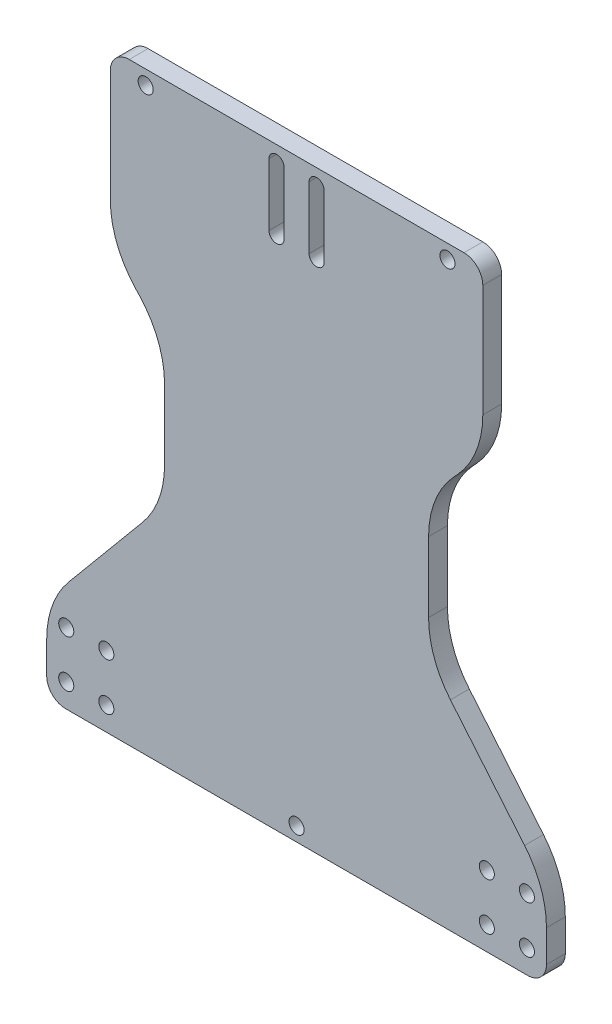
SolidWorks part; units mm, degrees
material "Acrylic (Medium-high impact)"
ref_plane "Front Plane" through (0, 0, 0) normal (0, 0, 1) x (1, 0, 0)
ref_plane "Top Plane" through (0, 0, 0) normal (0, 1, 0) x (1, 0, 0)
ref_plane "Right Plane" through (0, 0, 0) normal (1, 0, 0) x (0, 0, -1)
sketch "Sketch1" plane through (0, 0, 0) normal (0, 0, 1) x (1, 0, 0)
  line L0 (-0.75, 63) -> (106.75, 63) construction
  line L1 (0, 0) -> (106, 0)
  line L2 (0, 0) -> (0, 18)
  line L3 (81, 48) -> (81, 78)
  line L4 (106, 18) -> (81, 48)
  line L5 (0, 18) -> (25, 48)
  line L6 (25, 48) -> (25, 78)
  line L7 (106, 0) -> (106, 18)
  line L8 (53, 0) -> (53, 63) construction
  line L9 (13.5, 126) -> (13.5, 90.3404)
  line L10 (13.5, 90.3404) -> (25, 78)
  line L11 (92.5, 90.3404) -> (81, 78)
  line L12 (92.5, 126) -> (92.5, 90.3404)
  line L13 (13.5, 126) -> (92.5, 126)
  line L14 (12.65, 10) -> (4.15, 10) construction
  line L15 (4.15, 5) -> (12.65, 5) construction
  line L16 (4.15, 5) -> (4.15, 15) construction
  line L17 (4.15, 15) -> (12.65, 15) construction
  line L18 (12.65, 5) -> (12.65, 15) construction
  line L19 (53, 126) -> (53, 122.6) construction
  line L20 (48.75, 122.6) -> (57.25, 122.6) construction
  line L21 (48.75, 122.6) -> (48.75, 109.4) construction
  line L22 (48.75, 109.4) -> (57.25, 109.4) construction
  line L23 (57.25, 122.6) -> (57.25, 109.4) construction
  line L24 (48.75, 116) -> (57.25, 116) construction
  line L25 (48.75, 122.6) -> (48.75, 109.4) construction
  line L26 (50.35, 122.6) -> (50.35, 109.4)
  line L27 (47.15, 122.6) -> (47.15, 109.4)
  line L28 (57.25, 109.4) -> (57.25, 122.6) construction
  line L29 (55.65, 109.4) -> (55.65, 122.6)
  line L30 (58.85, 109.4) -> (58.85, 122.6)
  circle A0 centre (4.15, 5) radius 1.6
  circle A1 centre (12.65, 5) radius 1.6
  circle A2 centre (12.65, 15) radius 1.6
  circle A3 centre (4.15, 15) radius 1.6
  circle A4 centre (101.85, 5) radius 1.6
  circle A5 centre (93.35, 5) radius 1.6
  circle A6 centre (93.35, 15) radius 1.6
  circle A7 centre (101.85, 15) radius 1.6
  circle A8 centre (53, 3) radius 1.6
  circle A9 centre (21, 123) radius 1.6
  circle A10 centre (85, 123) radius 1.6
  arc A12 (50.35, 122.6) -> (47.15, 122.6) centre (48.75, 122.6) ccw
  arc A13 (47.15, 109.4) -> (50.35, 109.4) centre (48.75, 109.4) ccw
  arc A14 (55.65, 109.4) -> (58.85, 109.4) centre (57.25, 109.4) ccw
  arc A15 (58.85, 122.6) -> (55.65, 122.6) centre (57.25, 122.6) ccw
  point P16 (25, 63)
  point P18 (81, 63)
  point P51 (48.75, 116)
  point P56 (57.25, 116)
  dimension "D10" = 3.2
  dimension "D15" = 3.2
  dimension "D19" = 32
  dimension "D1" = 63
  dimension "D2" = 53
  dimension "D3" = 18
  dimension "D4" = 30
  dimension "D5" = 25
  dimension "D6" = 10
  dimension "D7" = 8.5
  dimension "D8" = 53
  dimension "D9" = 4.15
  dimension "D11" = 8.5
  dimension "D12" = 3
  dimension "D13" = 53
  dimension "D14" = 13.2
  dimension "D16" = 3
  dimension "D17" = 32
  dimension "D18" = 3
  dimension "D20" = 63
  dimension "D21" = 39.5
extrude "Boss-Extrude1" add sketch "Sketch1" along normal blind 4
fillet "Fillet1" radius 4 4 edges at (106, 0, 2) (0, 0, 2) (92.5, 126, 2) (13.5, 126, 2)
fillet "Fillet2" radius 20 8 edges at (81, 78, 2) (81, 48, 2) (106, 18, 2) (25, 78, 2) (25, 48, 2) (0, 18, 2) (92.5, 90.3404, 2) (13.5, 90.3404, 2)
